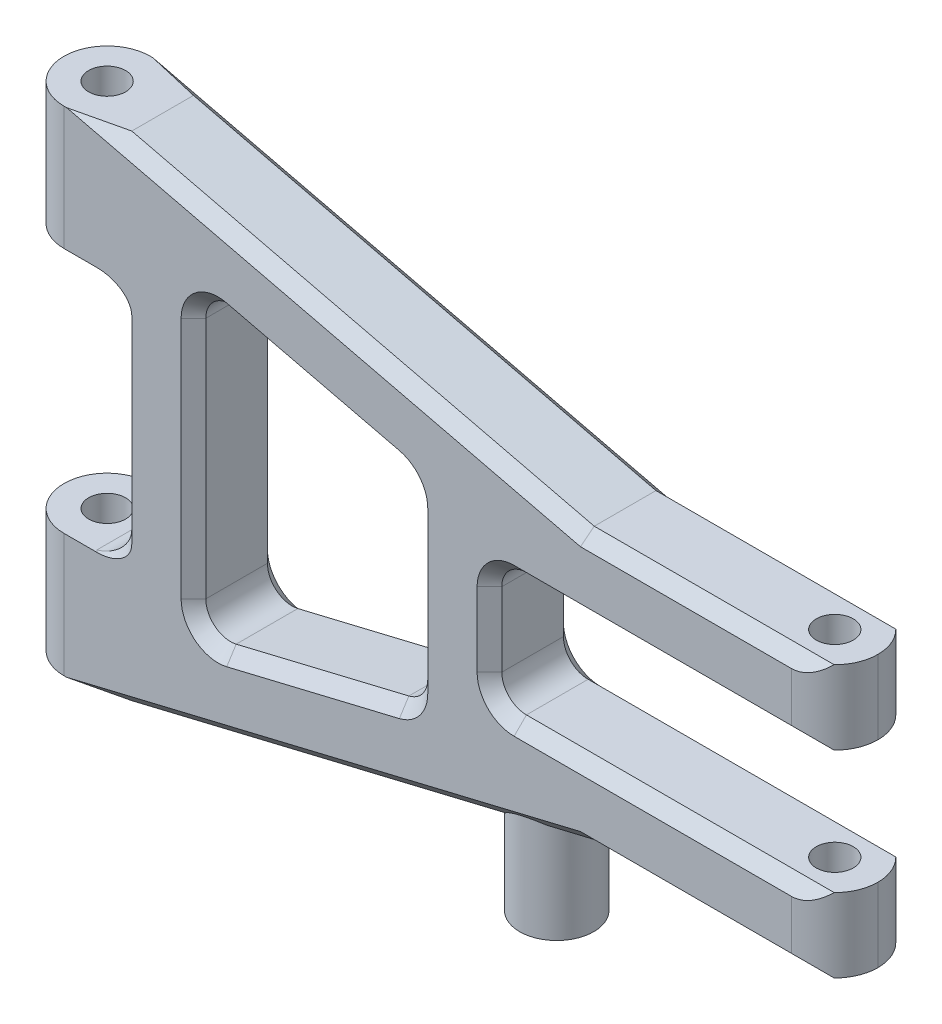
SolidWorks part; units mm, degrees
material "PBT General Purpose"
ref_plane "Front" through (0, 0, 0) normal (0, 0, 1) x (1, 0, 0)
ref_plane "Top" through (0, 0, 0) normal (0, 1, 0) x (1, 0, 0)
ref_plane "Right" through (0, 0, 0) normal (1, 0, 0) x (0, 0, -1)
sketch "Sketch2" plane through (0, 0, 0) normal (0, 0, 1) x (1, 0, 0)
  line L0 (0, 0) -> (0, 10)
  line L1 (8, 20) -> (14, 20) construction
  line L2 (66, 25) -> (66, 31) construction
  line L3 (66, 31) -> (66, 25)
  line L4 (66, 9) -> (45.5, 9)
  line L5 (0, 0) -> (8, 0)
  line L6 (8, 0) -> (45.5, 9)
  line L7 (45.5, 9) -> (45.5, 15) construction
  line L8 (66, 31) -> (45.5, 31)
  line L9 (8, 0) -> (8, 47.0859) construction
  line L10 (0, 40) -> (8, 40)
  line L11 (8, 40) -> (45.5, 31)
  line L12 (0, 10) -> (8, 10)
  line L13 (0, 30) -> (8, 30)
  line L14 (8, 30) -> (8, 10)
  line L15 (0, 30) -> (0, 40)
  line L16 (66, 15) -> (38, 15)
  line L17 (66, 25) -> (32, 25) construction
  line L18 (38, 15) -> (38, 25)
  line L19 (38, 25) -> (66, 25)
  line L20 (66, 15) -> (66, 9)
  line L21 (45.5, 25) -> (45.5, 35.8171) construction
  line L22 (32, 34.24) -> (32, 5.76) construction
  line L23 (14, 42.6279) -> (14, -3.8567) construction
  line L24 (14, 38.56) -> (11682.6476, 48657.9251) construction
  line L25 (-212.7361, -985.4937) -> (26.3184, 10.5668) construction
  line L26 (12.5998, 32.7257) -> (48631.9649, -11635.9219) construction
  line L27 (14, 1.44) -> (11.3675, 12.4088) construction
  line L28 (12.5998, 7.2743) -> (48631.9649, 11675.9219) construction
  line L29 (14, 32.3896) -> (14, 7.6104)
  line L30 (14, 7.6104) -> (32, 11.9304)
  line L31 (32, 11.9304) -> (32, 28.0696)
  line L32 (32, 28.0696) -> (14, 32.3896)
  line L33 (32, 20) -> (38, 20) construction
  line L34 (30.5998, 28.4057) -> (11700.6476, 48653.6051) construction
  point P3 (66, 25)
  point P13 (0, 10)
  point P16 (0, 30)
  point P20 (66, 15)
  point P25 (32, 20)
  dimension "D1" = 40
  dimension "D2" = 6
  dimension "D3" = 6
  dimension "D4" = 22
  dimension "D5" = 20.5
  dimension "D6" = 8
  dimension "D7" = 10
  dimension "D8" = 10
  dimension "D9" = 6
  dimension "D10" = 28
  dimension "D11" = 6
  dimension "D12" = 6
  dimension "D13" = 6
extrude "Boss-Extrude1" add sketch "Sketch2" along normal blind 3.5 and the other way blind 3.5
fillet "Fillet1" radius 3.5 8 edges at (66, 28, -3.5) (66, 28, 3.5) (66, 12, -3.5) (66, 12, 3.5) (0, 5, -3.5) (0, 5, 3.5) (0, 35, -3.5) (0, 35, 3.5)
fillet "Fillet3" radius 2 2 edges at (38, 15, 0) (38, 25, 0)
fillet "Fillet4" radius 2 4 edges at (14, 7.6104, 0) (14, 32.3896, 0) (32, 28.0696, 0) (32, 11.9304, 0)
chamfer "Chamfer1" distance 1 angle 45 2 edges at (8, 20, -3.5) (8, 20, 3.5)
fillet "Fillet5" radius 2 6 edges at (8.5, 10, -3) (8, 10, 0) (8.5, 10, 3) (8.5, 30, -3) (8.5, 30, 3) (8, 30, 0)
chamfer "Chamfer2" distance 1 angle 45 16 edges at (14, 20, -3.5) (14.7618, 8.5766, -3.5) (14.7618, 31.4234, -3.5) (23.4667, 9.8824, -3.5) (23.4667, 30.1176, -3.5) (31.5706, 12.2689, -3.5) (31.5706, 27.7311, -3.5) (32, 20, -3.5) (14, 20, 3.5) (14.7618, 8.5766, 3.5) (14.7618, 31.4234, 3.5) (23.4667, 9.8824, 3.5) (23.4667, 30.1176, 3.5) (31.5706, 12.2689, 3.5) (31.5706, 27.7311, 3.5) (32, 20, 3.5)
chamfer "Chamfer4" distance 1 angle 45 8 edges at (26.75, 4.5, -3.5) (54, 9, -3.5) (54, 9, 3.5) (26.75, 4.5, 3.5) (26.75, 35.5, -3.5) (54, 31, -3.5) (54, 31, 3.5) (26.75, 35.5, 3.5) tangent propagation no
chamfer "Chamfer5" distance 1 angle 45 10 edges at (51.25, 15, -3.5) (38.5858, 15.5858, -3.5) (38, 20, -3.5) (51.25, 25, -3.5) (38.5858, 24.4142, -3.5) (51.25, 25, 3.5) (38.5858, 24.4142, 3.5) (51.25, 15, 3.5) (38.5858, 15.5858, 3.5) (38, 20, 3.5) tangent propagation no
sketch "Sketch3" plane through (0, 31, 0) normal (0, 1, 0) x (1, 0, 0)
  line L0 (45.3817, 3.5) -> (62.5, 3.5) construction
  circle A0 centre (62.5, 0) radius 1.5
  dimension "D1" = 3
  dimension "D2" = 3.5
  dimension "D3" = 3.5
extrude "Cut-Extrude1" cut sketch "Sketch3" against normal up to surface (22 mm away) up to face at (57.4806, 9, 0)
sketch "Sketch4" plane through (0, 40, 0) normal (0, 1, 0) x (1, 0, 0)
  circle A0 centre (3.5, 0) radius 1.5
  dimension "D1" = 3
  dimension "D2" = 3.5
extrude "Cut-Extrude2" cut sketch "Sketch4" against normal up to surface (40 mm away) up to face at (4.14, 0, 0)
sketch "Sketch6" plane through (0, 0, 0) normal (0, 1, 0) x (1, 0, 0)
  circle A0 centre (39.9538, 0) radius 3
extrude "Boss-Extrude2" add sketch "Sketch6" along normal up to vertex (10 mm away) up to point (45.3817, 10, 3.5)
sketch "Sketch7" plane through (0, 0, 0) normal (0, -1, 0) x (1, 0, 0)
  line L0 (39.9538, 0) -> (39.9538, 3) construction
  arc A0 (41.6122, 2.5) -> (38.2955, 2.5) centre (39.9538, 0) ccw construction
  circle A1 centre (39.9538, 0) radius 1.25
  dimension "D1" = 2.5
extrude "Cut-Extrude3" cut sketch "Sketch7" against normal blind 5
cosmetic thread "Cosmetic Thread1" parameters "D2"=3
